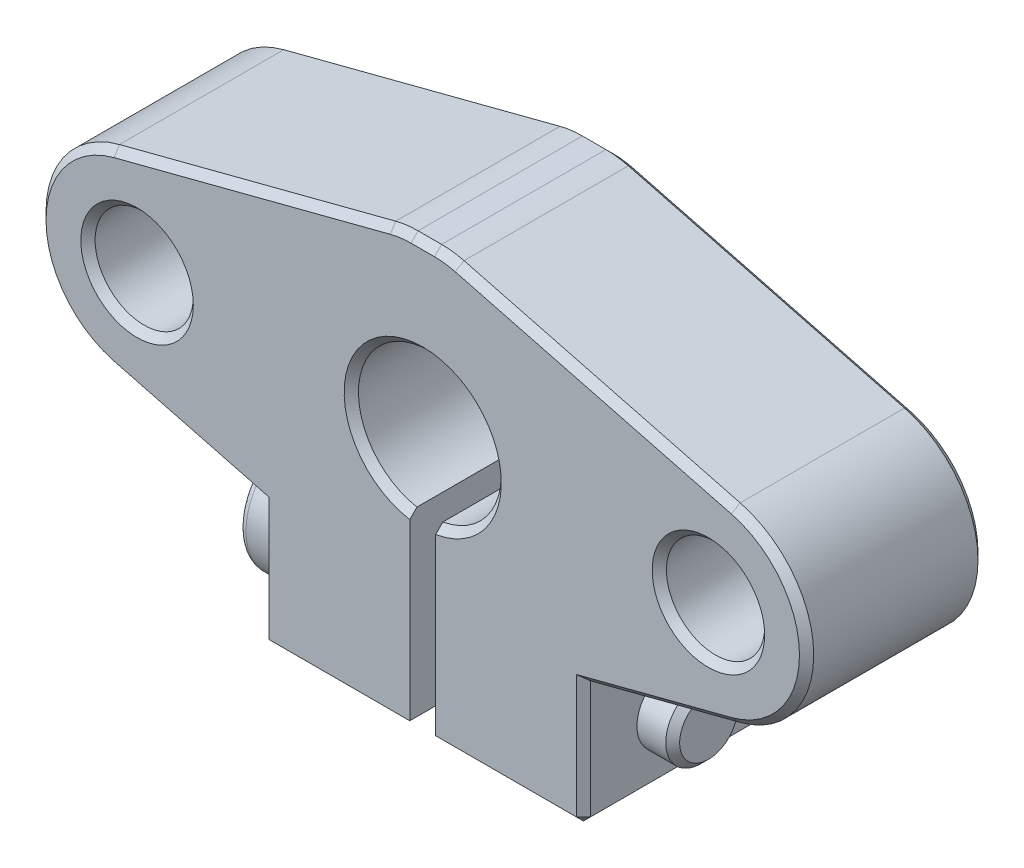
SolidWorks part; units mm, degrees
ref_plane "Спереди" through (0, 0, 0) normal (0, 0, 1) x (1, 0, 0)
ref_plane "Сверху" through (0, 0, 0) normal (0, 1, 0) x (1, 0, 0)
ref_plane "Справа" through (0, 0, 0) normal (1, 0, 0) x (0, 0, -1)
sketch "Эскиз2" plane through (0, 0, 0) normal (0, 0, 1) x (1, 0, 0)
  line L0 (-16, 0) -> (16, 0) construction
  line L1 (9, 7.5) -> (1.2976, 9.5)
  line L2 (9, 7.5) -> (17.3823, 5.3235)
  line L3 (0, 14.1459) -> (0, -18.2907) construction
  line L4 (9, -7.5) -> (17.3823, -5.3235)
  line L5 (-9, -14.5) -> (9, -14.5)
  line L6 (9, -14.5) -> (9, -7.5)
  line L7 (9, -11) -> (-9, -11) construction
  line L8 (1.2976, 9.5) -> (-1.2976, 9.5)
  line L9 (21.5, 0) -> (21.5, -6.4867) construction
  line L10 (0.725, -3.9337) -> (0.725, -14.5)
  line L11 (-21.5, 0) -> (-21.5, -6.4867) construction
  line L12 (-0.725, -3.9337) -> (-0.725, -14.5)
  line L13 (-9, -14.5) -> (-9, -7.5)
  line L14 (-9, -7.5) -> (-17.3823, -5.3235)
  line L15 (-9, 7.5) -> (-17.3823, 5.3235)
  line L16 (-9, 7.5) -> (-1.2976, 9.5)
  circle A0 centre (0, 0) radius 4
  circle A1 centre (16, 0) radius 2.4
  circle A2 centre (16, 0) radius 2.75
  circle A3 centre (16, 0) radius 5.5
  circle A4 centre (-16, 0) radius 5.5
  circle A5 centre (-16, 0) radius 2.75
  circle A6 centre (-16, 0) radius 2.4
  point P27 (0, -11)
  point P33 (0, 9.5)
  point P35 (0, -14.5)
  dimension "D1" = 4.8
  dimension "D2" = 5.5
  dimension "D3" = 11
  dimension "D4" = 8
  dimension "D5" = 16
  dimension "D6" = 9
  dimension "D7" = 11
  dimension "D8" = 24
  dimension "D9" = 21.5
  dimension "D10" = 7
  dimension "D11" = 1.45
extrude "Бобышка-Вытянуть1" add sketch "Эскиз2" along normal blind 10 contours L15 A4 L14 L13 L5 L12 A0 L10 L6 L4 A3 L2 L1 L8 L16 | A3 A2 | A4 A5 region at (13.085, 6.0028, 0) region at (20.2274, 3.2699, 0) region at (-12.7301, 4.2274, 0)
sketch "Эскиз4" plane through (-9, 0, 0) normal (-1, 0, 0) x (0, 0, 1)
  line L0 (0, -14.5) -> (10, -7.5) construction
  circle A0 centre (5, -11) radius 2
  dimension "D1" = 4
fillet "Скругление1" radius 5 2 edges at (-1.2976, 9.5, 5) (1.2976, 9.5, 5)
chamfer "Фаска1" distance 0.4 angle 45 34 edges at (-13.25, 0, 10) (18.75, 0, 10) (0.725, -14.5, 5) (9, -14.5, 5) (-9, -14.5, 5) (-21.5, 0, 0) (-13.1911, -6.4117, 0) (-4.8625, -14.5, 0) (-9.649, 7.3315, 0) (0, 9.5, 0) (9.649, 7.3315, 0) (21.5, 0, 0) (13.1911, -6.4117, 0) (4.8625, -14.5, 0) (0, 4, 0) (-0.725, -14.5, 5) (0, 9.5, 10) (9.649, 7.3315, 10) (21.5, 0, 10) (13.1911, -6.4117, 10) (9, -11, 10) (4.8625, -14.5, 10) (0, 4, 10) (-4.8625, -14.5, 10) (-13.1911, -6.4117, 10) (-21.5, 0, 10) (-9.649, 7.3315, 10) (-1.2924, 9.4597, 0) (1.2924, 9.4597, 0) (1.2924, 9.4597, 10) (-1.2924, 9.4597, 10) (-9, -11, 10) (-13.25, 0, 0) (18.75, 0, 0)
sketch "Эскиз6" plane through (0, 0, 10) normal (0, 0, 1) x (1, 0, 0)
  line L0 (-8.6, -11) -> (-10.2537, -10.0452)
  line L1 (-10.2537, -10.0452) -> (-10.2537, -11.9548)
  line L2 (-10.2537, -11.9548) -> (-8.6, -11)
  line L3 (-9, -14.5) -> (-9, -7.5) construction
  point P5 (-9, -11)
  dimension "D1" = 0.4
extrude "Вырез-Вытянуть3" cut sketch "Эскиз6" against normal up to next
extrude "Вырез-Вытянуть1" cut sketch "Эскиз4" against normal through all contours A0
ref_plane "Плоскость1" through (0, 0, 5) normal (0, 0, 1) x (1, 0, 0)
sketch "Эскиз7" plane through (0, 0, 5) normal (0, 0, 1) x (1, 0, 0)
  line L0 (-8.6, -11) -> (14.2, -11) construction
  line L1 (-11.8, -11) -> (-11.8, -7.5)
  line L2 (-11.8, -7.5) -> (-9, -7.5)
  line L3 (-9, -7.5) -> (-9, -9)
  line L4 (-9, -9) -> (10.61, -9)
  line L5 (11, -9.39) -> (11, -11)
  line L6 (11, -11) -> (-11.8, -11)
  line L7 (11, -9.39) -> (10.61, -9)
  line L8 (-9, -10.7691) -> (-9, -7.5) construction
  line L9 (-8.3, 1.4588) -> (-8.3, -4.8912) construction
  line L10 (-3, 1.4588) -> (-3, -4.8912) construction
  line L11 (-49, 1.4588) -> (-49, -4.8912) construction
  dimension "D1" = 2.8
  dimension "D2" = 20
  dimension "D3" = 45
  dimension "D6" = 0.7
  dimension "D7" = 14
  dimension "D8" = 60
  dimension "D9" = 2
  dimension "D10" = 1.61
  dimension "D11" = 3.5
revolve "Повернуть1" add sketch "Эскиз7" angle 360 about L6
fillet "Скругление2" radius 0.4 1 edges at (-11.8, -7.5, 5)
sketch "Эскиз8" plane through (-11.8, 0, 0) normal (-1, 0, 0) x (0, 0, 1)
  line L1 (5, -9.2679) -> (3.5, -10.134)
  line L2 (3.5, -10.134) -> (3.5, -11.866)
  line L3 (3.5, -11.866) -> (5, -12.7321)
  line L4 (5, -12.7321) -> (6.5, -11.866)
  line L5 (6.5, -11.866) -> (6.5, -10.134)
  line L6 (6.5, -10.134) -> (5, -9.2679)
  circle A0 centre (5, -11) radius 1.5 construction
  dimension "D1" = 3
extrude "Вырез-Вытянуть4" cut sketch "Эскиз8" against normal blind 2.5
chamfer "Фаска2" distance 0.4 angle 45 12 edges at (-11.8, -9.701, 4.25) (-11.8, -11, 3.5) (-11.8, -12.299, 4.25) (-11.8, -12.299, 5.75) (-11.8, -11, 6.5) (-11.8, -9.701, 5.75) (-9.3, -11, 6.5) (-9.3, -12.299, 5.75) (-9.3, -12.299, 4.25) (-9.3, -11, 3.5) (-9.3, -9.701, 4.25) (-9.3, -9.701, 5.75)
ref_axis "Ось1" through (0, 0, 9.6) along (0, 0, -1)
